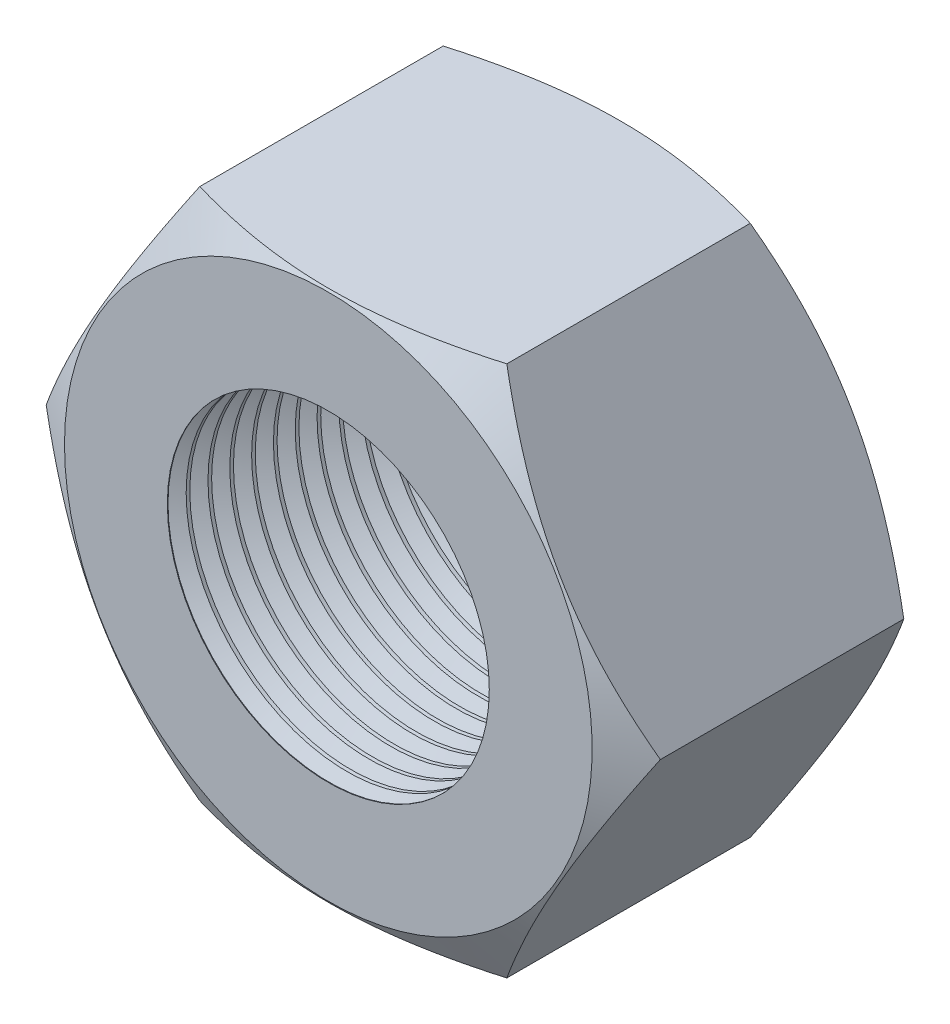
SolidWorks part; units mm, degrees
ref_plane "Front" through (0, 0, 0) normal (0, 0, 1) x (1, 0, 0)
ref_plane "Top" through (0, 0, 0) normal (0, 1, 0) x (1, 0, 0)
ref_plane "Right" through (0, 0, 0) normal (1, 0, 0) x (0, 0, -1)
sketch "Sketch1" plane through (0, 0, 0) normal (0, 0, 1) x (1, 0, 0)
  line L1 (27.4241, -47.5) -> (54.8483, 0)
  line L2 (54.8483, 0) -> (27.4241, 47.5)
  line L3 (27.4241, 47.5) -> (-27.4241, 47.5)
  line L4 (-27.4241, 47.5) -> (-54.8483, 0)
  line L5 (-54.8483, 0) -> (-27.4241, -47.5)
  line L6 (-27.4241, -47.5) -> (27.4241, -47.5)
  circle A0 centre (0, 0) radius 47.5 construction
  circle A1 centre (0, 0) radius 28.7525
extrude "BaseNut" add sketch "Sketch1" against normal blind 52.4
cosmetic thread "ThreadCosmetic1" [suppressed] parameters "D"=64
sketch "Sketch2" plane through (0, 0, 0) normal (0, 1, 0) x (1, 0, 0)
  line L0 (-54.8483, 52.4) -> (-47.125, 52.4)
  line L2 (-47.125, 52.4) -> (-54.8483, 47.941)
  line L3 (-54.8483, 47.941) -> (-54.8483, 52.4)
  line L4 (0, 3.3759) -> (0, -9.8171) construction
  line L6 (-9.7712, 26.2) -> (9.8853, 26.2) construction
  line L7 (-54.8483, 4.459) -> (-54.8483, 0)
  line L8 (-47.125, 0) -> (-54.8483, 4.459)
  line L9 (-54.8483, 0) -> (-47.125, 0)
  line L10 (-54.8483, 52.4) -> (-54.8483, 0) construction
  dimension "D1" = 30
  dimension "D2" = 26.2
revolve "Double-Chamfer" cut sketch "Sketch2" angle 360 about L4
sketch "Sketch4" plane through (0, 0, 0) normal (0, 1, 0) x (1, 0, 0)
  line L0 (31.5649, 52.4) -> (28.7525, 50.7762)
  line L1 (28.7525, 50.7762) -> (25.505, 50.7762)
  line L2 (25.505, 50.7762) -> (25.505, 54.0237)
  line L3 (25.505, 54.0237) -> (28.7525, 54.0237)
  line L4 (28.7525, 54.0237) -> (31.5649, 52.4)
  line L5 (0, 0) -> (0, 109.7681) construction
  dimension "D1" = 3.2475
  dimension "D2" = 57.505
revolve "Cut-Revolve10" cut sketch "Sketch4" angle 360 about L5
pattern_linear "LPattern10" count 14 spacing 3.897 along (0, 0, 1) of "Cut-Revolve10"
equation "\"dw@Sketch2\" = \"s@Sketch1\"-0.75"
equation "\"D2@Sketch2\" = \"m@BaseNut\" / 2"
equation "\"D2@Sketch4\"=\"D@Sketch1\""
equation "\"D1@Sketch4\" =  (\"D@ThreadCosmetic1\" - \"D2@Sketch4\"  )  / 2"
equation "\"D3@LPattern10\" = \"D1@Sketch4\" * 1.2"
equation "\"D1@LPattern10\" = \"m@BaseNut\" / \"D3@LPattern10\" + 1"
